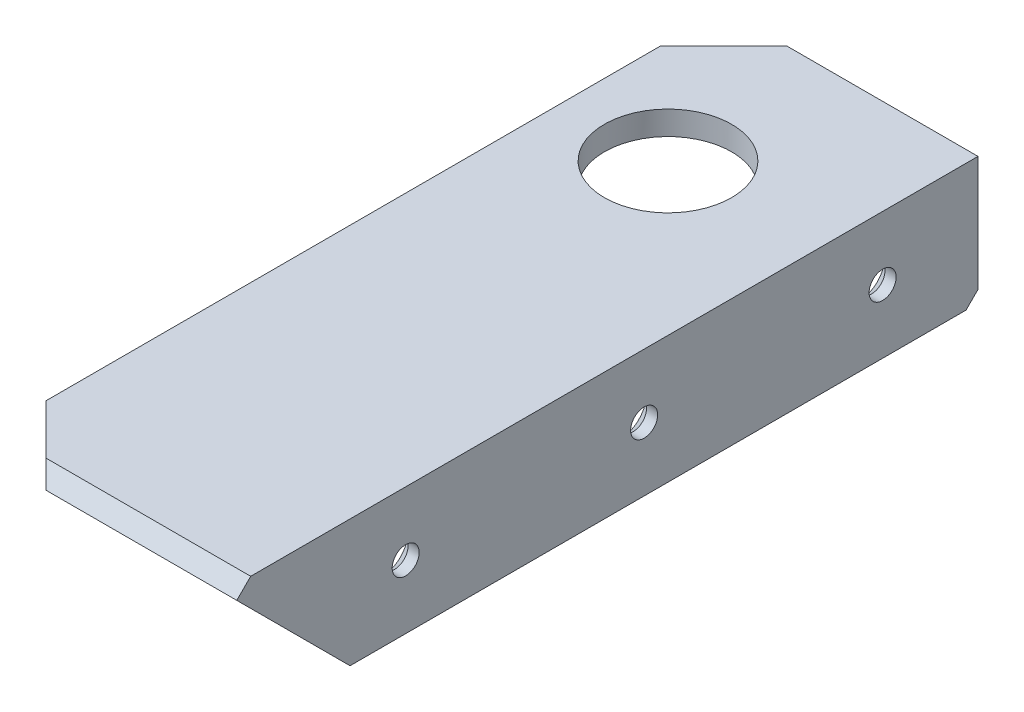
SolidWorks part; units mm, degrees
ref_plane "前视基准面" through (0, 0, 0) normal (0, 0, 1) x (1, 0, 0)
ref_plane "上视基准面" through (0, 0, 0) normal (0, 1, 0) x (1, 0, 0)
ref_plane "右视基准面" through (0, 0, 0) normal (1, 0, 0) x (0, 0, -1)
sketch "草图1" plane through (0, 0, 0) normal (0, 0, 1) x (1, 0, 0)
  line L0 (0, 0) -> (0, 13)
  line L1 (0, 13) -> (-29, 13)
  line L2 (-29, 13) -> (-29, 16)
  line L3 (-29, 16) -> (3, 16)
  line L4 (3, 16) -> (3, 0)
  line L5 (3, 0) -> (0, 0)
  dimension "D1" = 3
  dimension "D2" = 3
  dimension "D3" = 16
  dimension "D4" = 32
extrude "凸台-拉伸1" add sketch "草图1" along normal blind 95
sketch "草图2" plane through (3, 0, 0) normal (1, 0, 0) x (0, 0, -1)
  line L0 (-95, 16) -> (-95, 0)
  line L1 (-95, 0) -> (-79, 0)
  line L2 (-95, 0) -> (0, 0) construction
  line L3 (-79, 0) -> (-95, 16)
  dimension "D1" = 16
extrude "切除-拉伸1" cut sketch "草图2" against normal through all
chamfer "倒角1" distance 3.5 angle 45 1 edges at (-13, 16, 95) first distance on face at (-13, 16, 47.5)
chamfer "倒角3" distance 1.5 angle 45 1 edges at (1.5, 0, 0)
sketch "草图7" plane through (0, 16, 0) normal (0, 1, 0) x (1, 0, 0)
  line L0 (-29, -91.5) -> (-29, 0) construction
  line L1 (3, 0) -> (-29, 0) construction
  circle A0 centre (-16, -20) radius 8
  dimension "D1" = 16
  dimension "D2" = 13
  dimension "D3" = 20
extrude "切除-拉伸3" cut sketch "草图7" against normal through all
hole_wizard "打孔尺寸(%根据十字)槽沉头木螺钉的类型1" positions "草图9" profile "草图8" countersink size "M3" standard "GB" end condition through all
sketch "草图9" plane through (0, 0, 0) normal (-1, 0, 0) x (0, 0, 1)
  line L0 (0, 13) -> (0, 1.5) construction
  line L1 (79, 0) -> (1.5, 0) construction
  point P0 (12, 8)
  point P2 (42, 8)
  point P4 (72, 8)
  dimension "D1" = 30
  dimension "D2" = 30
  dimension "D3" = 12
  dimension "D4" = 8
sketch "草图8" plane through (0, 8, 12) normal (0, 1, 0) x (0, 0, 1)
  line L0 (0, 0) -> (0, 3)
  line L1 (0, 3) -> (1.7, 3)
  line L2 (1.7, 3) -> (1.7, 1.6)
  line L3 (1.7, 1.6) -> (3.3, 0)
  line L5 (3.3, 0) -> (0, 0)
  line L6 (-1.7, 1.6) -> (-3.3, 0) construction
  line L11 (0, -6.35) -> (0, 107.95) construction
  dimension "通孔孔直径" = 3.4
  dimension "通孔孔深度" = 3
  dimension "近端锥形沉头孔直径" = 6.6
  dimension "近端锥形沉头孔角度" = 90
fillet "圆角2" radius 3 1 edges at (0, 13, 46)
sketch "草图10" plane through (0, 16, 0) normal (0, 1, 0) x (1, 0, 0)
  line L0 (-29, -93.25) -> (-29, -85.25)
  line L1 (-29, -91.5) -> (-29, 0) construction
  line L2 (-29, -85.25) -> (-21, -93.25)
  line L3 (3, -93.25) -> (-29, -93.25) construction
  line L4 (-21, -93.25) -> (-29, -93.25)
  line L5 (-29, 0) -> (-29, -8)
  line L6 (-29, -91.5) -> (-29, 0) construction
  line L7 (-29, -8) -> (-21, 0)
  line L8 (3, 0) -> (-29, 0) construction
  line L9 (-21, 0) -> (-29, 0)
  dimension "D1" = 8
  dimension "D2" = 8
  dimension "D3" = 8
  dimension "D4" = 8
extrude "切除-拉伸4" cut sketch "草图10" against normal through all
